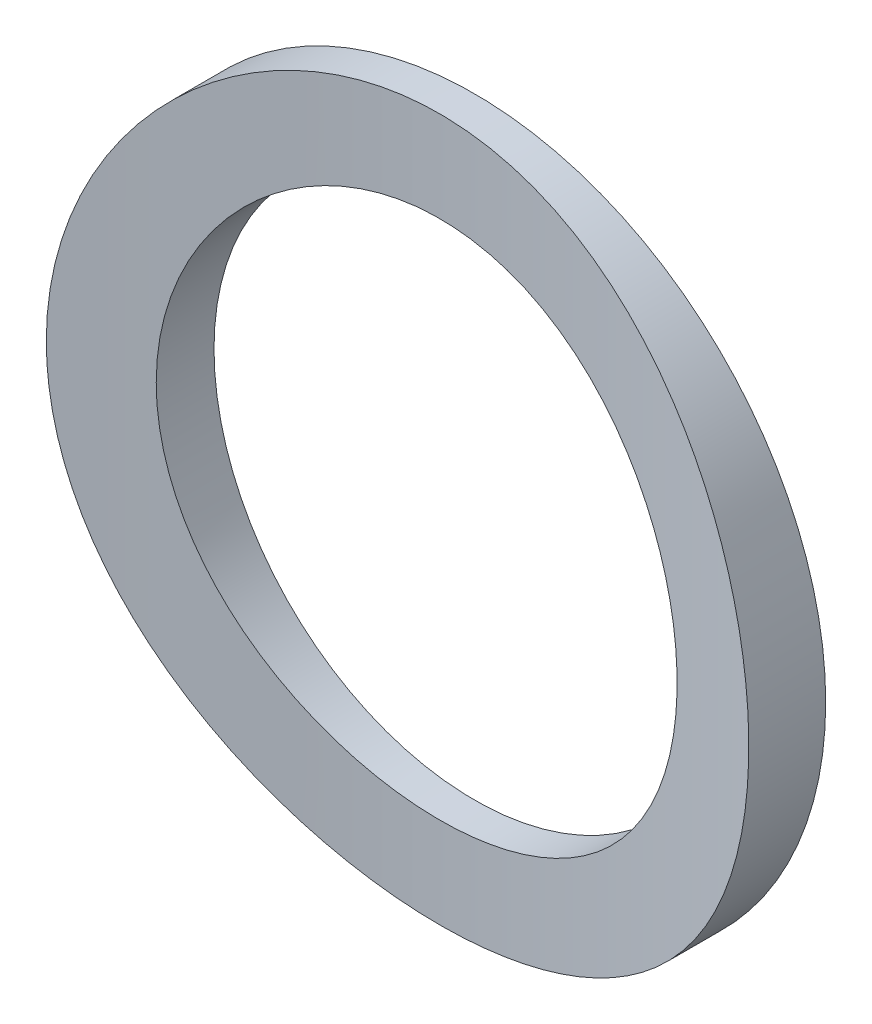
SolidWorks part; units mm, degrees
material "PTFE (general)"
ref_plane "Front Plane" through (0, 0, 0) normal (0, 0, 1) x (1, 0, 0)
ref_plane "Top Plane" through (0, 0, 0) normal (0, 1, 0) x (1, 0, 0)
ref_plane "Right Plane" through (0, 0, 0) normal (1, 0, 0) x (0, 0, -1)
sketch "Sketch1" plane through (0, 0, 0) normal (0, 0, 1) x (1, 0, 0)
  circle A0 centre (0, 0) radius 10.115
  circle A1 centre (0, 0) radius 7.5
  dimension "D1" = 20.23
  dimension "D2" = 15
extrude "Boss-Extrude1" add sketch "Sketch1" along normal blind 30
sketch "Sketch2" plane through (0, 0, 0) normal (0, 1, 0) x (1, 0, 0)
  line L0 (10.115, 0) -> (-10.115, 0) construction
  circle A0 centre (0, -43.725) radius 42.725
  dimension "D1" = 85.45
  dimension "D2" = 43.725
extrude "Cut-Extrude1" cut sketch "Sketch2" against normal through all both and the other way through all
